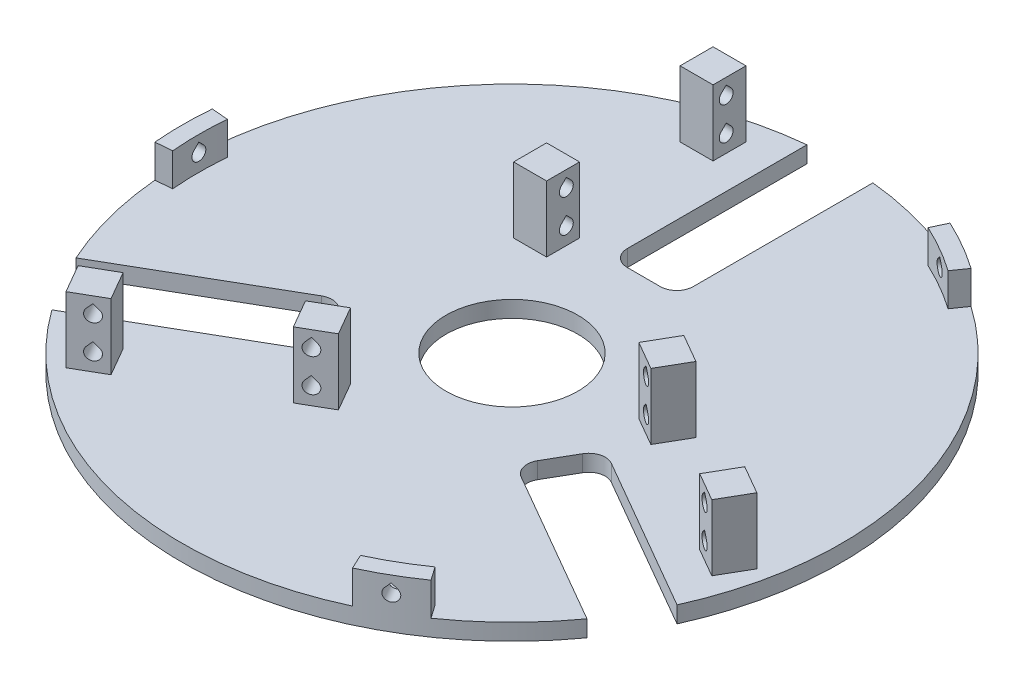
SolidWorks part; units mm, degrees
ref_plane "Front Plane" through (0, 0, 0) normal (0, 0, 1) x (1, 0, 0)
ref_plane "Top Plane" through (0, 0, 0) normal (0, 1, 0) x (1, 0, 0)
ref_plane "Right Plane" through (0, 0, 0) normal (1, 0, 0) x (0, 0, -1)
sketch "Sketch1" plane through (0, 0, 0) normal (0, 1, 0) x (1, 0, 0)
  circle A0 centre (0, 0) radius 100
  dimension "D1" = 200
extrude "Boss-Extrude1" add sketch "Sketch1" along normal blind 5
ref_plane "Plane1" through (0, 5, 0) normal (0, 1, 0) x (1, 0, 0)
sketch "Sketch2" plane through (0, 5, 0) normal (0, 1, 0) x (1, 0, 0)
  line L0 (0, 0) -> (0, 100) construction
  line L1 (0, 0) -> (-86.6025, -50) construction
  line L2 (0, 0) -> (86.6025, -50) construction
  line L4 (-30, 91) -> (-20, 91)
  line L5 (-30, 91) -> (-30, 81)
  line L6 (-30, 81) -> (-20, 81)
  line L7 (-20, 91) -> (-20, 81)
  line L8 (-30, 40.5) -> (-20, 40.5)
  line L9 (-30, 40.5) -> (-30, 30.5)
  line L10 (-30, 30.5) -> (-20, 30.5)
  line L11 (-20, 40.5) -> (-20, 30.5)
  line L19 (50.074, 5.7308) -> (45.074, -2.9295)
  line L20 (50.074, 5.7308) -> (41.4138, 10.7308)
  line L21 (41.4138, 10.7308) -> (36.4138, 2.0705)
  line L22 (45.074, -2.9295) -> (36.4138, 2.0705)
  line L23 (93.8083, -19.5192) -> (88.8083, -28.1795)
  line L24 (93.8083, -19.5192) -> (85.1481, -14.5192)
  line L25 (85.1481, -14.5192) -> (80.1481, -23.1795)
  line L26 (88.8083, -28.1795) -> (80.1481, -23.1795)
  line L27 (-20.074, -46.2308) -> (-25.074, -37.5705)
  line L28 (-20.074, -46.2308) -> (-11.4138, -41.2308)
  line L29 (-11.4138, -41.2308) -> (-16.4138, -32.5705)
  line L30 (-25.074, -37.5705) -> (-16.4138, -32.5705)
  line L31 (-63.8083, -71.4808) -> (-68.8083, -62.8205)
  line L32 (-63.8083, -71.4808) -> (-55.1481, -66.4808)
  line L33 (-55.1481, -66.4808) -> (-60.1481, -57.8205)
  line L34 (-68.8083, -62.8205) -> (-60.1481, -57.8205)
  circle A0 centre (0, 0) radius 100 construction
  point P34 (0, 0)
  dimension "D1" = 120
  dimension "D2" = 120
  dimension "D3" = 20
  dimension "D4" = 40.5
  dimension "D5" = 10
  dimension "D6" = 10
  dimension "D7" = 10
  dimension "D8" = 30.5
  dimension "D9" = 3
extrude "Boss-Extrude2" add sketch "Sketch2" along normal blind 20
ref_plane "Plane2" through (-20, 0, 0) normal (1, 0, 0) x (0, 0, -1)
sketch "Sketch3" plane through (-20, 0, 0) normal (1, 0, 0) x (0, 0, -1)
  line L0 (81, 25) -> (81, 5) construction
  line L1 (81, 25) -> (91, 25) construction
  line L2 (40.5, 25) -> (40.5, 5) construction
  line L4 (83.5151, 21.4849) -> (85, 22.9698)
  line L5 (85, 22.9698) -> (86.4849, 21.4849)
  line L6 (83.5151, 11.4849) -> (85, 12.9698)
  line L7 (85, 12.9698) -> (86.4849, 11.4849)
  line L9 (30.5, 25) -> (40.5, 25) construction
  line L10 (36.5, 22.9698) -> (35.0151, 21.4849)
  line L11 (36.5, 22.9698) -> (37.9849, 21.4849)
  line L12 (36.5, 12.9698) -> (35.0151, 11.4849)
  line L13 (36.5, 12.9698) -> (37.9849, 11.4849)
  arc A0 (83.5151, 21.4849) -> (86.4849, 21.4849) centre (85, 20) ccw
  arc A4 (83.5151, 11.4849) -> (86.4849, 11.4849) centre (85, 10) ccw
  arc A5 (35.0151, 21.4849) -> (37.9849, 21.4849) centre (36.5, 20) ccw
  arc A6 (35.0151, 11.4849) -> (37.9849, 11.4849) centre (36.5, 10) ccw
  dimension "D1" = 4.2
  dimension "D7" = 4.2
  dimension "D2" = 4
  dimension "D3" = 5
  dimension "D4" = 2
  dimension "D5" = 10
  dimension "D6" = 90
  dimension "D8" = 4
  dimension "D9" = 5
  dimension "D10" = 90
  dimension "D12" = 10
  dimension "D11" = 2
extrude "Cut-Extrude1" cut sketch "Sketch3" against normal up to next
ref_plane "Plane3" through (10, 0, 17.3205) normal (-0.5, 0, -0.866) x (-0.866, 0, 0.5)
sketch "Sketch4" plane through (10, 0, 17.3205) normal (-0.5, 0, -0.866) x (-0.866, 0, 0.5)
  line L1 (40.5, 25) -> (40.5, 5) construction
  line L2 (30.5, 25) -> (40.5, 25) construction
  line L3 (81, 25) -> (81, 5) construction
  line L5 (36.5, 22.9698) -> (35.0151, 21.4849)
  line L6 (36.5, 22.9698) -> (37.9849, 21.4849)
  line L7 (36.5, 12.9698) -> (35.0151, 11.4849)
  line L8 (36.5, 12.9698) -> (37.9849, 11.4849)
  line L9 (81, 25) -> (91, 25) construction
  line L11 (85, 22.9698) -> (83.5151, 21.4849)
  line L12 (85, 22.9698) -> (86.4849, 21.4849)
  line L13 (85, 12.9698) -> (83.5151, 11.4849)
  line L14 (85, 12.9698) -> (86.4849, 11.4849)
  arc A2 (35.0151, 21.4849) -> (37.9849, 21.4849) centre (36.5, 20) ccw
  arc A4 (35.0151, 11.4849) -> (37.9849, 11.4849) centre (36.5, 10) ccw
  arc A5 (83.5151, 21.4849) -> (86.4849, 21.4849) centre (85, 20) ccw
  arc A6 (83.5151, 11.4849) -> (86.4849, 11.4849) centre (85, 10) ccw
  dimension "D1" = 4.2
  dimension "D9" = 4.2
  dimension "D2" = 4
  dimension "D3" = 5
  dimension "D4" = 90
  dimension "D5" = 2
  dimension "D6" = 10
  dimension "D7" = 5
  dimension "D8" = 4
  dimension "D10" = 90
  dimension "D12" = 10
  dimension "D11" = 2
extrude "Cut-Extrude2" cut sketch "Sketch4" against normal up to next
ref_plane "Plane4" through (10, 0, -17.3205) normal (-0.5, 0, 0.866) x (0.866, 0, 0.5)
sketch "Sketch5" plane through (10, 0, -17.3205) normal (-0.5, 0, 0.866) x (0.866, 0, 0.5)
  line L0 (30.5, 25) -> (40.5, 25) construction
  line L2 (40.5, 25) -> (40.5, 5) construction
  line L4 (36.5, 22.9698) -> (35.0151, 21.4849)
  line L5 (36.5, 22.9698) -> (37.9849, 21.4849)
  line L6 (36.5, 12.9698) -> (35.0151, 11.4849)
  line L7 (36.5, 12.9698) -> (37.9849, 11.4849)
  line L8 (81, 25) -> (81, 5) construction
  line L9 (81, 25) -> (91, 25) construction
  line L10 (85, 22.9698) -> (83.5151, 21.4849)
  line L11 (85, 22.9698) -> (86.4849, 21.4849)
  line L12 (85, 12.9698) -> (83.5151, 11.4849)
  line L13 (85, 12.9698) -> (86.4849, 11.4849)
  arc A2 (35.0151, 21.4849) -> (37.9849, 21.4849) centre (36.5, 20) ccw
  arc A4 (35.0151, 11.4849) -> (37.9849, 11.4849) centre (36.5, 10) ccw
  arc A5 (83.5151, 21.4849) -> (86.4849, 21.4849) centre (85, 20) ccw
  arc A6 (83.5151, 11.4849) -> (86.4849, 11.4849) centre (85, 10) ccw
  dimension "D3" = 4.2
  dimension "D9" = 4.2
  dimension "D1" = 5
  dimension "D2" = 4
  dimension "D4" = 90
  dimension "D5" = 2
  dimension "D6" = 10
  dimension "D7" = 4
  dimension "D8" = 5
  dimension "D10" = 90
  dimension "D12" = 10
  dimension "D11" = 2
extrude "Cut-Extrude3" cut sketch "Sketch5" against normal up to next
sketch "Sketch8" plane through (0, 0, 0) normal (0, 1, 0) x (1, 0, 0)
  line L3 (0, 0) -> (0, 100) construction
  line L19 (37.141, -15.6699) -> (32.141, -24.3301)
  line L20 (-5, 40) -> (5, 40)
  line L21 (-10, 45) -> (-10, 105)
  line L22 (-10, 105) -> (10, 105)
  line L44 (10, 45) -> (10, 105)
  line L45 (43.9711, -13.8397) -> (95.9327, -43.8397)
  line L46 (95.9327, -43.8397) -> (85.9327, -61.1603)
  line L47 (33.9711, -31.1603) -> (85.9327, -61.1603)
  line L48 (-32.141, -24.3301) -> (-37.141, -15.6699)
  line L49 (-33.9711, -31.1603) -> (-85.9327, -61.1603)
  line L50 (-85.9327, -61.1603) -> (-95.9327, -43.8397)
  line L51 (-43.9711, -13.8397) -> (-95.9327, -43.8397)
  circle A0 centre (0, 0) radius 20
  circle A1 centre (0, 0) radius 100 construction
  arc A2 (5, 40) -> (10, 45) centre (5, 45) ccw
  arc A3 (-5, 40) -> (-10, 45) centre (-5, 45) cw
  arc A4 (32.141, -24.3301) -> (33.9711, -31.1603) centre (36.4711, -26.8301) ccw
  arc A5 (37.141, -15.6699) -> (43.9711, -13.8397) centre (41.4711, -18.1699) cw
  arc A6 (-37.141, -15.6699) -> (-43.9711, -13.8397) centre (-41.4711, -18.1699) ccw
  arc A7 (-32.141, -24.3301) -> (-33.9711, -31.1603) centre (-36.4711, -26.8301) cw
  point P32 (0, 0)
  dimension "D1" = 40
  dimension "D6" = 3
  dimension "D5" = 10
  dimension "D3" = 5
  dimension "D2" = 40
  dimension "D4" = 10
extrude "Cut-Extrude7" cut sketch "Sketch8" along normal up to next
ref_plane "Plane8" through (0, 5, 0) normal (0, 1, 0) x (1, 0, 0)
sketch "Sketch14" plane through (0, 5, 0) normal (0, 1, 0) x (1, 0, 0)
  line L0 (0, 0) -> (-100, 0) construction
  line L1 (-99.6195, 8.7156) -> (-94.6385, 8.2798)
  line L2 (-99.6195, -8.7156) -> (-94.6385, -8.2798)
  line L3 (57.3576, 81.9152) -> (54.4898, 77.8194)
  line L4 (42.2618, 90.6308) -> (40.1487, 86.0992)
  line L5 (42.2618, -90.6308) -> (40.1487, -86.0992)
  line L6 (57.3576, -81.9152) -> (54.4898, -77.8194)
  arc A0 (-10, 99.4987) -> (-91.1684, -41.0891) centre (0, 0) ccw construction
  arc A1 (-99.6195, 8.7156) -> (-99.6195, -8.7156) centre (0, 0) ccw
  arc A2 (-94.6385, 8.2798) -> (-94.6385, -8.2798) centre (0, 0) ccw
  arc A3 (57.3576, 81.9152) -> (42.2618, 90.6308) centre (0, 0) ccw
  arc A4 (54.4898, 77.8194) -> (40.1487, 86.0992) centre (0, 0) ccw
  arc A5 (42.2618, -90.6308) -> (57.3576, -81.9152) centre (0, 0) ccw
  arc A6 (40.1487, -86.0992) -> (54.4898, -77.8194) centre (0, 0) ccw
  point P21 (0, 0)
  dimension "D3" = 190
  dimension "D1" = 5
  dimension "D2" = 5
  dimension "D4" = 3
extrude "Boss-Extrude4" add sketch "Sketch14" along normal blind 10
ref_plane "Plane9" through (-100, 0, 0) normal (-1, 0, 0) x (0, 0, 1)
sketch "Sketch15" plane through (-100, 0, 0) normal (-1, 0, 0) x (0, 0, 1)
  line L0 (8.7156, 15) -> (-8.7156, 15) construction
  line L1 (0, 12.9698) -> (-1.4849, 11.4849)
  line L2 (0, 12.9698) -> (1.4849, 11.4849)
  arc A0 (-1.4849, 11.4849) -> (1.4849, 11.4849) centre (0, 10) ccw
  dimension "D1" = 4.2
  dimension "D2" = 5
  dimension "D3" = 90
extrude "Cut-Extrude11" cut sketch "Sketch15" against normal blind 10 and the other way blind 10
ref_plane "Plane10" through (50, 0, 86.6025) normal (0.5, 0, 0.866) x (0.866, 0, -0.5)
sketch "Sketch16" plane through (50, 0, 86.6025) normal (0.5, 0, 0.866) x (0.866, 0, -0.5)
  line L0 (8.7156, 15) -> (-8.7156, 15) construction
  line L1 (-1.4849, 11.4849) -> (0, 12.9698)
  line L2 (0, 12.9698) -> (1.4849, 11.4849)
  arc A0 (-1.4849, 11.4849) -> (1.4849, 11.4849) centre (0, 10) ccw
  dimension "D1" = 4.2
  dimension "D2" = 5
  dimension "D3" = 90
extrude "Cut-Extrude12" cut sketch "Sketch16" against normal blind 10 and the other way blind 10
ref_plane "Plane11" through (50, 0, -86.6025) normal (0.5, 0, -0.866) x (-0.866, 0, -0.5)
sketch "Sketch17" plane through (50, 0, -86.6025) normal (0.5, 0, -0.866) x (-0.866, 0, -0.5)
  line L0 (8.7156, 15) -> (-8.7156, 15) construction
  line L1 (-1.4849, 11.4849) -> (0, 12.9698)
  line L2 (0, 12.9698) -> (1.4849, 11.4849)
  arc A0 (-1.4849, 11.4849) -> (1.4849, 11.4849) centre (0, 10) ccw
  dimension "D1" = 4.2
  dimension "D2" = 5
  dimension "D3" = 90
extrude "Cut-Extrude13" cut sketch "Sketch17" against normal blind 10 and the other way blind 10
ref_plane "Plane5" through (-100, 0, 0) normal (-1, 0, 0) x (0, 0, 1)
ref_plane "Plane6" through (50, 0, 86.6025) normal (0.5, 0, 0.866) x (0.866, 0, -0.5)
ref_plane "Plane7" through (50, 0, -86.6025) normal (0.5, 0, -0.866) x (-0.866, 0, -0.5)
